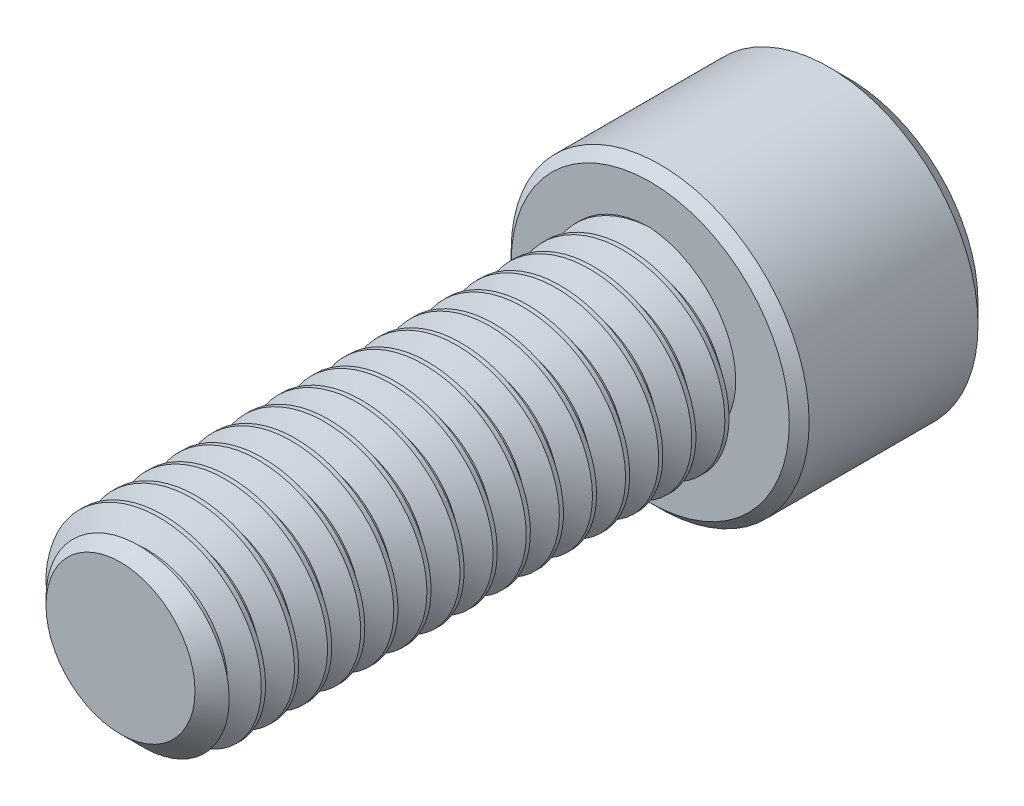
SolidWorks part; units mm, degrees
ref_plane "Front Plane" through (0, 0, 0) normal (0, 0, 1) x (1, 0, 0)
ref_plane "Top Plane" through (0, 0, 0) normal (0, 1, 0) x (1, 0, 0)
ref_plane "Right Plane" through (0, 0, 0) normal (1, 0, 0) x (0, 0, -1)
sketch "Sketch1" plane through (0, 0, 0) normal (0, 0, 1) x (1, 0, 0)
  line L0 (0, 4.7625) -> (0, -4.7625) construction
  circle A0 centre (0, 0) radius 4.7625
  dimension "OD" = 9.525
extrude "Extrude1" add sketch "Sketch1" against normal blind 25.4
sketch "Sketch2" plane through (0, 0, 0) normal (0, 0, 1) x (1, 0, 0)
  circle A0 centre (0, 0) radius 4.7625 construction
  circle A1 centre (0, 0) radius 4.7625
curve "Helix/Spiral1" pitch 1.5875 height 26.9875 turns 17 parameters "pitch"=1.5875
chamfer "Chamfer3" distance 1.1906 angle 45 1 edges at (4.7625, 0, 0)
sketch "Sketch3" plane through (0, 0, 0) normal (1, 0, 0) x (0, 0, -1)
  line L0 (-1.3891, 4.7625) -> (-0.7938, 3.7314)
  line L1 (-0.7938, 3.7314) -> (-0.5953, 3.7314)
  line L2 (-0.5953, 3.7314) -> (0, 4.7625)
  line L3 (-1.3891, 4.7625) -> (0, 4.7625)
  line L4 (-0.6945, 4.7625) -> (-0.6945, 3.7314) construction
  line L5 (-1.0914, 4.2469) -> (-0.2977, 4.2469) construction
  line L6 (0, 4.7625) -> (0, -4.7625) construction
  dimension "D1" = 0.1984
  dimension "D2" = 0.7937
  dimension "D3" = 60
sweep "Cut-Sweep1" cut profiles "Sketch3" path "Helix/Spiral1"
sketch "Sketch6" plane through (0, 0, -25.4) normal (0, 0, -1) x (-1, 0, 0)
  circle A0 centre (0, 0) radius 7.1438
  dimension "head dia" = 14.2875
extrude "Extrude2" add sketch "Sketch6" along normal blind 9.525
sketch "Sketch7" plane through (0, 0, -34.925) normal (0, 0, -1) x (-1, 0, 0)
  line L1 (0, 4.5827) -> (-3.9688, 2.2914)
  line L2 (-3.9688, 2.2914) -> (-3.9688, -2.2914)
  line L3 (-3.9688, -2.2914) -> (0, -4.5827)
  line L4 (0, -4.5827) -> (3.9688, -2.2914)
  line L5 (3.9688, -2.2914) -> (3.9687, 2.2914)
  line L6 (3.9687, 2.2914) -> (0, 4.5827)
  circle A0 centre (0, 0) radius 3.9688 construction
  dimension "hex dia" = 7.9375
extrude "Cut-Extrude1" cut sketch "Sketch7" against normal blind 5.9531
sketch "Sketch8" plane through (0, 0, -34.925) normal (0, 0, -1) x (-1, 0, 0)
  circle A0 centre (0, 0) radius 4.5827
extrude "Cut-Extrude2" cut sketch "Sketch8" against normal blind 0.9525 draft 45
chamfer "Chamfer1" distance 0.9525 angle 45 1 edges at (-7.1438, 0, -34.925)
chamfer "Chamfer2" distance 0.4763 angle 45 1 edges at (-7.1438, 0, -25.4)
sketch "Sketch9" plane through (0, 0, 0) normal (1, 0, 0) x (0, 0, -1)
  line L0 (0, 4.7625) -> (0, -4.7625) construction
  line L1 (8.7313, 4.7625) -> (8.7313, -4.7625) construction
  line L2 (25.4, 7.1437) -> (25.4, -7.1438) construction
  line L3 (34.925, 7.1437) -> (34.925, -7.1438) construction
  line L4 (34.925, 0) -> (0, 0) construction
  dimension "D1" = 8.7312
  dimension "D2" = 9.525
  dimension "D3" = 14.2875
  dimension "D4" = 25.4
equation "\"D3@Helix/Spiral1\" = \"screw length@Extrude1\"+\"pitch@Helix/Spiral1\""
equation "\"D1@Sketch3\" = \"pitch@Helix/Spiral1\"*.125"
equation "\"D2@Sketch3\" = \"pitch@Helix/Spiral1\"*.5"
equation "\"D1@Cut-Extrude1\" = \"hex dia@Sketch7\"*.75"
equation "\"D1@Chamfer1\" = \"head depth@Extrude2\"/10"
equation "\"D1@Sketch9\" = \"pitch@Helix/Spiral1\"*5.5"
equation "\"D1@Chamfer2\" = \"D1@Chamfer1\"/2"
equation "\"D1@Cut-Extrude2\" = \"D1@Chamfer2\"*2"
equation "\"D1@Chamfer3\" = \"pitch@Helix/Spiral1\"*.750"
equation "\"D2@Sketch9\" = \"head depth@Extrude2\""
equation "\"D3@Sketch9\" = \"head dia@Sketch6\""
equation "\"D4@Sketch9\" = \"screw length@Extrude1\""
